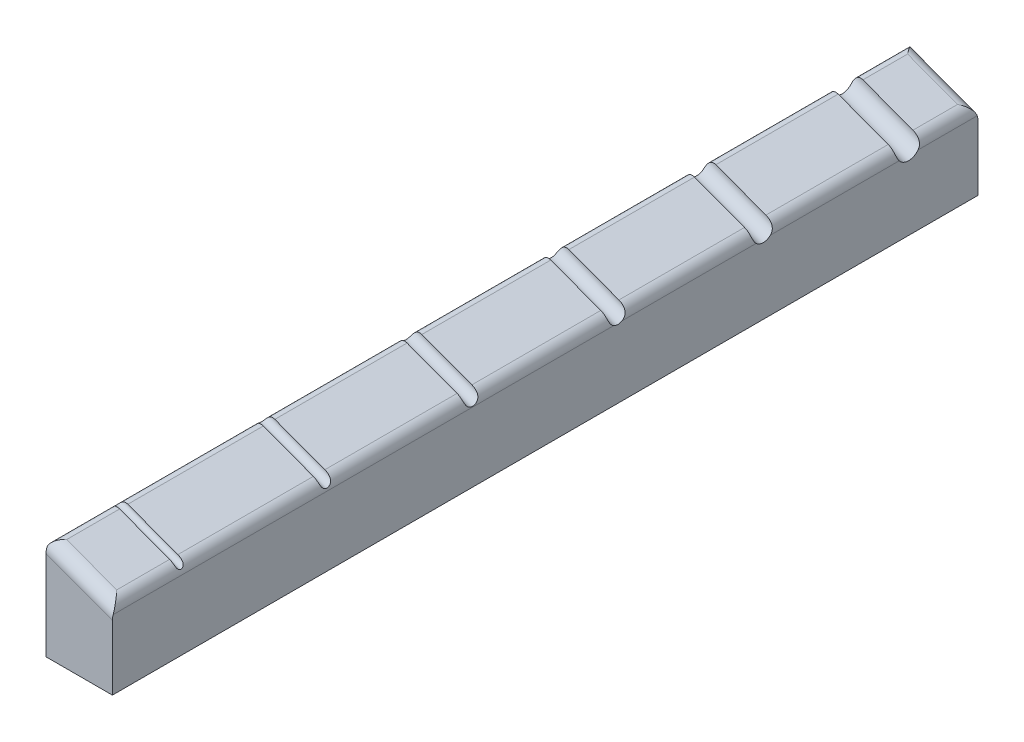
SolidWorks part; units mm, degrees
ref_plane "Front Plane" through (0, 0, 0) normal (0, 0, 1) x (1, 0, 0)
ref_plane "Top Plane" through (0, 0, 0) normal (0, 1, 0) x (1, 0, 0)
ref_plane "Right Plane" through (0, 0, 0) normal (1, 0, 0) x (0, 0, -1)
sketch "Sketch1" plane through (0, 0, 0) normal (0, 1, 0) x (1, 0, 0)
  line L1 (0, 0) -> (3.22, 0)
  line L2 (0, 0) -> (0, -41.98)
  line L3 (0, -41.98) -> (3.22, -41.98)
  line L4 (3.22, 0) -> (3.22, -41.98)
  dimension "D1" = 41.98
  dimension "D2" = 3.22
extrude "Boss-Extrude1" add sketch "Sketch1" along normal blind 4.98
sketch "Sketch2" plane through (0, 0, 41.98) normal (0, 0, 1) x (1, 0, 0)
  line L0 (0, 4.98) -> (3.22, 4.98)
  line L1 (3.22, 4.98) -> (3.22, 3.78)
  line L2 (3.22, 4.98) -> (3.22, 0) construction
  line L3 (3.22, 3.78) -> (0, 4.98)
extrude "Cut-Extrude1" cut sketch "Sketch2" against normal up to surface (41.98 mm away) up to face at (1.61, 2.49, 0)
sketch "Sketch3" plane through (1.6296, 4.3727, 0) normal (0.3492, 0.937, 0) x (0.937, -0.3492, 0)
  line L0 (-1.7391, 0) -> (-1.7391, -41.98) construction
  line L1 (-1.7391, -3.365) -> (-1.7391, -38.615) construction
  line L2 (-1.7391, -3.365) -> (3.0173, -3.365) construction
  line L3 (3.0173, -41.98) -> (3.0173, 0) construction
  line L28 (-1.7391, -10.415) -> (3.0173, -10.415) construction
  line L29 (-1.7391, -17.465) -> (3.0173, -17.465) construction
  line L30 (-1.7391, -24.515) -> (3.0173, -24.515) construction
  line L31 (-1.7391, -31.565) -> (3.0173, -31.565) construction
  line L32 (-1.7391, -38.615) -> (3.0173, -38.615) construction
ref_axis "Axis1" through (0, 4.98, 0) along (0, 0, 1)
ref_plane "Plane1" through (-1.6296, 0.6073, 0) normal (-0.937, 0.3492, 0) x (0, 0, 1)
fillet "Fillet1" radius 0.6 3 edges at (3.22, 3.78, 20.99) (1.61, 4.38, 0) (1.61, 4.38, 41.98)
fillet "Fillet2" radius 0.3 1 edges at (0, 4.98, 20.99) tangent propagation no
sketch "Sketch4" plane through (-1.6296, 0.6073, 0) normal (-0.937, 0.3492, 0) x (0, 0, 1)
  circle A0 centre (3.365, 4.6665) radius 0.6
  circle A1 centre (38.615, 4.6665) radius 0.2
  circle A2 centre (31.565, 4.6665) radius 0.28
  circle A3 centre (24.515, 4.6665) radius 0.36
  circle A4 centre (17.465, 4.6665) radius 0.44
  circle A5 centre (10.415, 4.6665) radius 0.52
extrude "Cut-Extrude2" cut sketch "Sketch4" against normal blind 4.98
